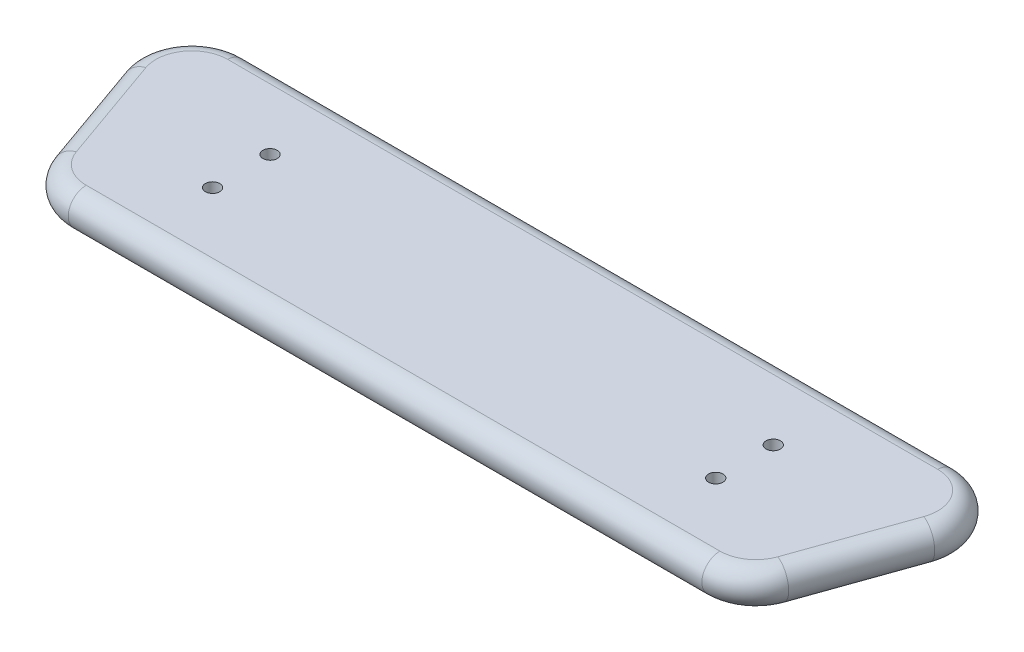
SolidWorks part; units mm, degrees
ref_plane "Front Plane" through (0, 0, 0) normal (0, 0, 1) x (1, 0, 0)
ref_plane "Top Plane" through (0, 0, 0) normal (0, 1, 0) x (1, 0, 0)
ref_plane "Right Plane" through (0, 0, 0) normal (1, 0, 0) x (0, 0, -1)
sketch "Sketch1" plane through (0, 0, 0) normal (0, 1, 0) x (1, 0, 0)
  line L0 (-112.9151, 9.9929) -> (-102.2916, -20.0071)
  line L1 (-88.1519, -30) -> (88.1519, -30)
  line L3 (-98.7755, 30) -> (98.7755, 30)
  line L7 (0, -33) -> (0, 33) construction
  line L8 (112.9151, 9.9929) -> (102.2916, -20.0071)
  arc A0 (98.7755, 30) -> (112.9151, 9.9929) centre (98.7755, 15) cw
  arc A1 (102.2916, -20.0071) -> (88.1519, -30) centre (88.1519, -15) cw
  arc A2 (-102.2916, -20.0071) -> (-88.1519, -30) centre (-88.1519, -15) ccw
  arc A3 (-112.9151, 9.9929) -> (-98.7755, 30) centre (-98.7755, 15) cw
  point P0 (0, 0)
  point P10 (120, 30)
  point P13 (98.7529, -30)
  point P16 (-98.7529, -30)
  point P19 (-120, 30)
  dimension "D2" = 15
  dimension "D1" = 240
  dimension "D3" = 70.5
extrude "Boss-Extrude2" add sketch "Sketch1" along normal blind 10 contours L3 A0 L8 A1 L1 A2 L0 A3
fillet "Fillet2" 16 edges at (-111.0251, 10, -23.6572) (-107.6033, 10, 5.0071) (-96.8091, 10, 27.2496) (0, 10, 30) (96.8091, 10, 27.2496) (107.6033, 10, 5.0071) (111.0251, 10, -23.6572) (0, 10, -30) (-111.0251, 0, -23.6572) (-107.6033, 0, 5.0071) (-96.8091, 0, 27.2496) (0, 0, 30) (96.8091, 0, 27.2496) (107.6033, 0, 5.0071) (111.0251, 0, -23.6572) (0, 0, -30) type full round first side face at (0, 10, 2.1499) second side face at (0, 0, 2.1499) middle face at (0, 5, -30) middle face at (-108.4352, 5, -21.8268) middle face at (-96.0154, 5, 26.1266) middle face at (-107.6033, 5, 5.0071) middle face at (108.4352, 5, -21.8268) middle face at (107.6033, 5, 5.0071) middle face at (96.0154, 5, 26.1266) middle face at (0, 5, 30)
sketch "Sketch5" plane through (0, 10, 0) normal (0, 1, 0) x (1, 0, 0)
  line L0 (-5.5001, 0) -> (5.5001, 0) construction
  line L1 (0, -5.5001) -> (0, 5.5001) construction
  circle A0 centre (-70, 8) radius 2
  circle A1 centre (-70, -8) radius 2
  circle A2 centre (70, -8) radius 2
  circle A3 centre (70, 8) radius 2
  dimension "D1" = 8
  dimension "D2" = 70
extrude "Cut-Extrude3" cut sketch "Sketch5" against normal blind 8
